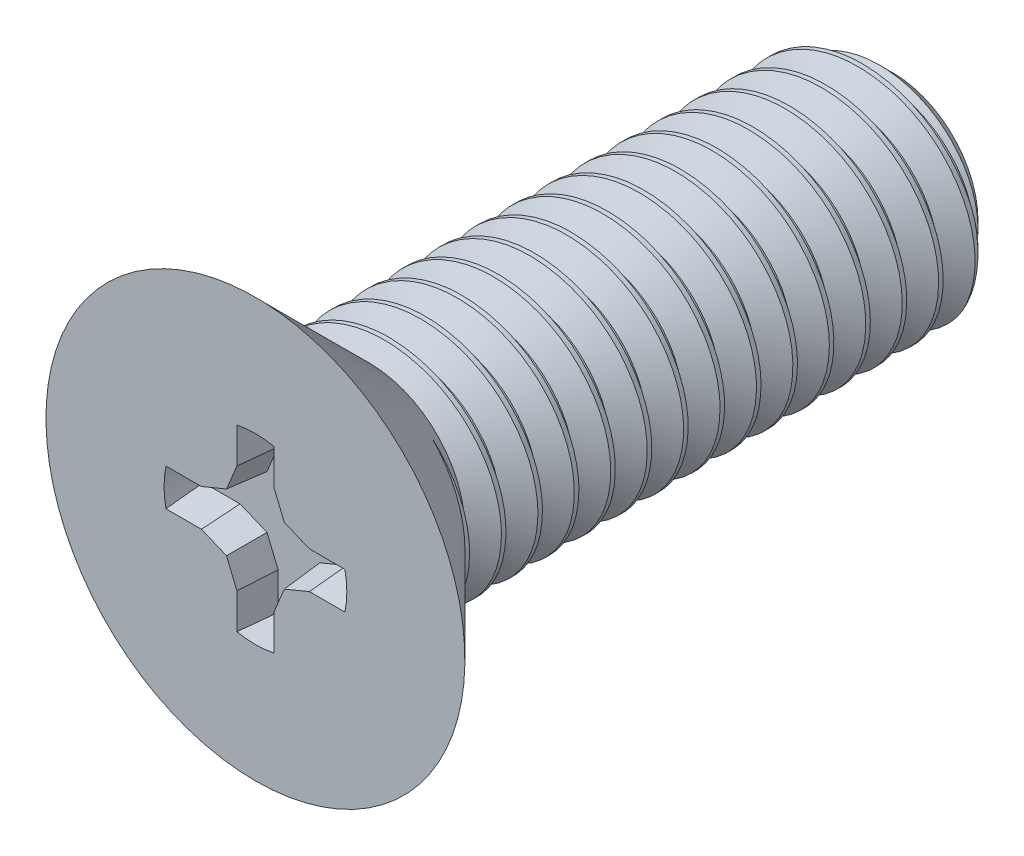
SolidWorks part; units mm, degrees
ref_plane "Front Plane" through (0, 0, 0) normal (0, 0, 1) x (1, 0, 0)
ref_plane "Top Plane" through (0, 0, 0) normal (0, 1, 0) x (1, 0, 0)
ref_plane "Right Plane" through (0, 0, 0) normal (1, 0, 0) x (0, 0, -1)
sketch "Sketch1" plane through (0, 0, 0) normal (1, 0, 0) x (0, 0, -1)
  line L0 (0, 0) -> (-2.5, 0) construction
  line L1 (-2.5, 4.6) -> (-2.5, -4.6) construction
  line L2 (-2.5, 4.6) -> (0, 2.1) construction
  line L3 (-2.5, -4.6) -> (0, -2.1) construction
  line L4 (0, 2.5) -> (0, -2.5) construction
  line L5 (0, 0) -> (11.5, 0) construction
  line L6 (0, 2.5) -> (0.8, 2.5) construction
  line L7 (0, 2.5) -> (-0.4, 2.5) construction
  line L8 (11.5, 2.1) -> (11.5, -2.1) construction
  point P6 (-2.5, 0)
  point P11 (0, 0)
  point P16 (-0.4, 2.5)
  point P17 (8.7, -2.5)
  point P20 (11.5, 0)
  point P21 (-1.25, 0)
  point P22 (8.7, -2.1)
  point P23 (11.5, -2.1)
  point P25 (11.5, 2.1)
  dimension "Head Height" = 2.5
  dimension "Head Diameter" = 9.2
  dimension "Countersink Angle" = 90
  dimension "Thread OD" = 5
  dimension "Length" = 14
  dimension "Thread Pitch" = 0.8
  dimension "D1" = 2.8
sketch "Sketch2" plane through (0, 0, 0) normal (0, 0, 1) x (1, 0, 0)
  line L0 (0.4064, 2.0066) -> (-0.4064, 2.0066) construction
  circle A0 centre (0, 0) radius 2.0066 construction
  point P3 (0, 2.0066)
  point P7 (0, 2.0066)
  dimension "Drive Dia" = 4.0132
  dimension "Drive Width" = 0.8128
sketch "Sketch3" plane through (0, 0, 0) normal (1, 0, 0) x (0, 0, -1)
  line L0 (-2.5, 0) -> (-2.5, 4.6)
  line L1 (-2.5, 4.6) -> (-0.4, 2.5)
  line L2 (-2.5, 4.6) -> (0, 2.1) construction
  line L3 (0, 2.5) -> (0.8, 2.5) construction
  line L4 (-2.5, 0) -> (-0.4, 0)
  line L5 (0, 0) -> (-2.5, 0) construction
  line L6 (-0.4, 0) -> (-0.4, 2.5)
revolve "Revolve1" add sketch "Sketch3" angle 360 about L4
sketch "Sketch5" plane through (0, 0, 0) normal (1, 0, 0) x (0, 0, -1)
  line L0 (11.5, 0) -> (-0.4, 0)
  line L1 (0, 0) -> (11.5, 0) construction
  line L2 (-0.4, 0) -> (-0.4, 2.5)
  line L3 (-0.4, 2.5) -> (10.868, 2.5)
  line L4 (10.868, 2.5) -> (11.5, 1.868)
  line L5 (11.5, 1.868) -> (11.5, 0)
  line L6 (10.868, 2.5) -> (11.5, 2.5) construction
  line L7 (11.5, 2.5) -> (11.5, 1.868) construction
  line L8 (0, 2.5) -> (0.8, 2.5) construction
  line L9 (-0.4, -2.5) -> (-0.4, 2.5) construction
  dimension "D1" = 0.632
revolve "Revolve2" add sketch "Sketch5" angle 360 about L0
sketch "Sketch4" plane through (0, 0, 2.5) normal (0, 0, 1) x (1, 0, 0)
  line L0 (0, 0) -> (0, 2.0066)
  line L1 (0, 0) -> (2.0066, 0)
  line L2 (0, 0) -> (1.1857, 1.1857) construction
  line L3 (0.4064, 1.965) -> (0.4064, 1.1857)
  line L4 (0.4064, 1.1857) -> (0.4064, 0.4064) construction
  line L5 (1.1857, 0.4064) -> (0.4064, 0.4064) construction
  line L6 (1.965, 0.4064) -> (1.1857, 0.4064)
  line L7 (0.4064, 1.1857) -> (0.6347, 0.6347)
  line L8 (0.6347, 0.6347) -> (1.1857, 0.4064)
  line L9 (0, 2.0066) -> (0, 4.6) construction
  line L10 (0, 4.6) -> (0, -4.6) construction
  circle A0 centre (0, 0) radius 2.0066 construction
  arc A1 (0, 2.0066) -> (0.4064, 1.965) centre (0, 0) cw
  arc A2 (2.0066, 0) -> (1.965, 0.4064) centre (0, 0) ccw
  arc A3 (1.1857, 0.4064) -> (0.4064, 1.1857) centre (1.1857, 1.1857) cw construction
  circle A4 centre (0, 0) radius 4.6 construction
  point P8 (0.6347, 0.6347)
  point P22 (0, -2.0066)
  point P23 (0, 2.0066)
  dimension "D1" = 2.5934
extrude "Cut-Extrude1" cut sketch "Sketch4" against normal blind 0.8333 contours L1 A2 L6 L8 L7 L3 A1 L0
pattern_circular "CirPattern1" count 4 over 360 about axis through (0, 0, 0) along (0, 0, 1) of "Cut-Extrude1"
draft "Draft2" type of draft neutral plane draft angle 5 faces to draft 16 face at (-1.5754, 0.4064, 2.0833) face at (-0.9102, 0.5205, 2.0833) face at (-0.5205, 0.9102, 2.0833) face at (-0.4064, 1.5754, 2.0833) face at (0.4064, 1.5754, 2.0833) face at (0.5205, 0.9102, 2.0833) face at (0.9102, 0.5205, 2.0833) face at (1.5754, 0.4064, 2.0833) face at (1.5754, -0.4064, 2.0833) face at (0.9102, -0.5205, 2.0833) face at (0.5205, -0.9102, 2.0833) face at (0.4064, -1.5754, 2.0833) face at (-0.4064, -1.5754, 2.0833) face at (-0.5205, -0.9102, 2.0833) face at (-0.9102, -0.5205, 2.0833) face at (-1.5754, -0.4064, 2.0833) neutral plane through (0, 0, 2.5) neutral plane normal (0, 0, 1) parameters "D1"=5
ref_plane "Plane1" through (0, 0, 0.4) normal (0, 0, -1) x (-1, 0, 0)
split "Split1" trim tools "Plane1" bodies to split 107 105 resulting bodies 108 109
sketch "Sketch6" plane through (0, 0, -11.5) normal (0, 0, 1) x (1, 0, 0)
  circle A1 centre (0, 0) radius 2.5
  circle A2 centre (0, 0) radius 2.5
  dimension "D1" = 0
curve "Helix/Spiral1" pitch 0.8 height 14 turns 17.5
sketch "Sketch7" plane through (0, 0, 0) normal (1, 0, 0) x (0, 0, -1)
  line L0 (11.45, 2.5866) -> (12.25, 2.5866) construction
  line L1 (11.45, 2.5866) -> (11.85, 1.8938) construction
  line L2 (11.85, 1.8938) -> (12.25, 2.5866) construction
  line L3 (11.8, 1.9804) -> (11.9, 1.9804) construction
  line L4 (11.5, 2.5) -> (12.2, 2.5) construction
  line L5 (11.85, 2.5) -> (11.85, 2.5866) construction
  line L6 (11.85, 1.9804) -> (11.85, 1.8938) construction
  line L7 (11.85, 2.5433) -> (11.475, 2.5433) construction
  line L10 (11.9, 1.9804) -> (11.8, 1.9804)
  line L11 (11.475, 2.5433) -> (11.8, 1.9804)
  line L12 (11.475, 2.5433) -> (12.225, 2.5433)
  line L13 (12.225, 2.5433) -> (11.9, 1.9804)
  dimension "D1" = 0.8
  dimension "D2" = 0.1
sweep "Cut-Sweep1" cut profiles "Sketch7" path "Helix/Spiral1" align with end faces yes
combine bodies "Combine1" operation type add bodies to combine 109 110
ref_plane "Plane2" through (0, 0, 0.4) normal (0, 0, 1) x (1, 0, 0)
sketch "Sketch8" plane through (0, 0, 0.4) normal (0, 0, 1) x (1, 0, 0)
  circle A0 centre (0, 0) radius 2.5
extrude "Boss-Extrude1" add sketch "Sketch8" against normal up to vertex draft 45
equation "\"D1@Sketch5\" = \"Thread Pitch@Sketch1\" * .79"
equation "\"D4@Helix/Spiral1\" = \"Thread Pitch@Sketch1\""
equation "\"D3@Helix/Spiral1\"=\"Length@Sketch1\""
equation "\"D1@Sketch7\" = \"Thread Pitch@Sketch1\""
equation "\"D2@Sketch7\" = \"Thread Pitch@Sketch1\" / 8"
equation "\"D1@Sketch1\"=\"Thread Pitch@Sketch1\"*3.5"
equation "\"D1@Cut-Extrude1\"=\"Head Height@Sketch1\"/3"
